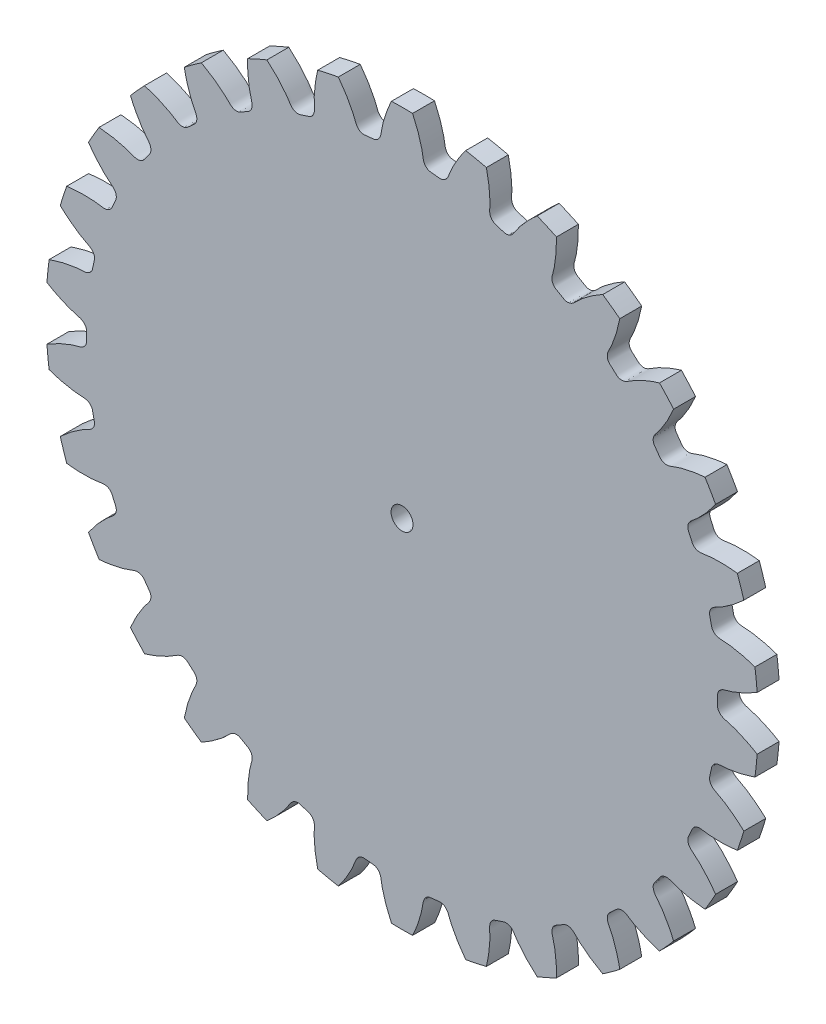
SolidWorks part; units mm, degrees
ref_plane "Front Plane" through (0, 0, 0) normal (0, 0, 1) x (1, 0, 0)
ref_plane "Top Plane" through (0, 0, 0) normal (0, 1, 0) x (1, 0, 0)
ref_plane "Right Plane" through (0, 0, 0) normal (1, 0, 0) x (0, 0, -1)
ref_axis "Axis1" through (0, 0, 4.4) along (0, 0, -1)
sketch "SketchRevolveGeartrax1Gear" plane through (0, 0, 0) normal (1, 0, 0) x (0, 0, -1)
  line L0 (0, 0) -> (1, 0) construction
  line L1 (-4, 0) -> (-4, 129.945)
  line L2 (-4, 129.945) -> (4, 129.945)
  line L3 (4, 129.945) -> (4, 0)
  line L4 (4, 0) -> (-4, 0)
  dimension "Side1" = 4
  dimension "OutsideRadius" = 129.945
  dimension "Side2" = 4
revolve "Geartrax1Gear" add sketch "SketchRevolveGeartrax1Gear" angle 360 about L0
sketch "SketchToothGeartrax1Gear" plane through (0, 0, 0) normal (0, 0, 1) x (1, 0, 0)
  arc A0 (129.894, 9.9432) -> (129.894, -9.9432) centre (0, 0) cw
  spline S0 degree 3 poles (129.894, -9.9432) (129.0232, -9.4093) (127.866, -8.7397) (126.4176, -7.9731) (125.6085, -7.5634) (124.8265, -7.1852) (124.0724, -6.8371) (123.3471, -6.5182) (122.6513, -6.2272) (121.9859, -5.963) (121.3515, -5.7243) (120.7489, -5.51) (120.1787, -5.3188) (119.6416, -5.1493) (119.1379, -5.001) (118.4579, -4.8106) (117.868, -4.6835) (117.3845, -4.5169) (117.1837, -4.4387) (116.982, -4.3493) (116.7778, -4.2461) (116.569, -4.1248) (116.3539, -3.9799) (116.1317, -3.8036) (115.9035, -3.5855) (115.6745, -3.3134) (115.4571, -2.9752) (115.2735, -2.5643) (115.1539, -2.1034) (115.1032, -1.2389) (115.1705, 0) (115.1032, 1.2389) (115.1539, 2.1034) (115.2735, 2.5643) (115.4571, 2.9752) (115.6745, 3.3134) (115.9035, 3.5855) (116.1317, 3.8036) (116.3539, 3.9799) (116.569, 4.1248) (116.7778, 4.2461) (116.982, 4.3493) (117.1837, 4.4387) (117.3845, 4.5169) (117.868, 4.6835) (118.4579, 4.8106) (119.1379, 5.001) (119.6416, 5.1493) (120.1787, 5.3188) (120.7489, 5.51) (121.3515, 5.7243) (121.9859, 5.963) (122.6513, 6.2272) (123.3471, 6.5182) (124.0724, 6.8371) (124.8265, 7.1852) (125.6085, 7.5634) (126.4176, 7.9731) (127.866, 8.7397) (129.0232, 9.4093) (129.894, 9.9432) knots 0 0 0 0 0.079652 0.104218 0.127792 0.150373 0.171961 0.192557 0.212161 0.230771 0.248389 0.265015 0.280648 0.295288 0.308936 0.321591 0.350362 0.355881 0.361459 0.367162 0.373074 0.379301 0.38598 0.393279 0.401398 0.410557 0.420947 0.432651 0.445522 0.457824 0.5 0.542176 0.554478 0.567349 0.579053 0.589443 0.598602 0.606721 0.61402 0.620699 0.626926 0.632838 0.638541 0.644119 0.649638 0.678409 0.691064 0.704712 0.719352 0.734985 0.751611 0.769229 0.787839 0.807443 0.828039 0.849627 0.872208 0.895782 0.920348 1 1 1 1
extrude "ToothExtrudeCutGeartrax1Gear" cut sketch "SketchToothGeartrax1Gear" against normal blind 4 and the other way blind 4
pattern_circular "PatternGeartrax1Gear" count 30 every 12 about axis through (0, 0, 4.4) along (0, 0, -1) of "ToothExtrudeCutGeartrax1Gear"
sketch "BoreRevolveSketch" plane through (0, 0, 0) normal (1, 0, 0) x (0, 0, -1)
  line L0 (0, 0) -> (1, 0) construction
  line L1 (-4, 0) -> (4, 0)
  line L2 (4, 0) -> (4, 4.05)
  line L3 (4, 4.05) -> (-4, 4)
  line L4 (-4, 4) -> (-4, 0)
  dimension "BoreSide1" = 4
  dimension "TaperSide1" = 4.05
  dimension "BoreSide2" = 4
  dimension "TaperSide2" = 4
revolve "BoreRevolveCut" cut sketch "BoreRevolveSketch" angle 360 about L0
sketch "AuxiliarySketchGeartrax1Gear" plane through (0, 0, 0) normal (0, 0, 1) x (1, 0, 0)
  circle A0 centre (0, 0) radius 123.3655 construction
  circle A1 centre (0, 0) radius 115.9257 construction
  circle A2 centre (0, 0) radius 118.1646 construction
  circle A3 centre (0, 0) radius 129.945 construction
  circle A4 centre (0, 0) radius 115.1411 construction
  dimension "PitchDiameter" = 246.731
  dimension "BaseDiameter" = 231.8513
  dimension "FormDiameter" = 236.3292
  dimension "MajorDiameter" = 259.89
  dimension "MinorDiameter" = 230.2823
